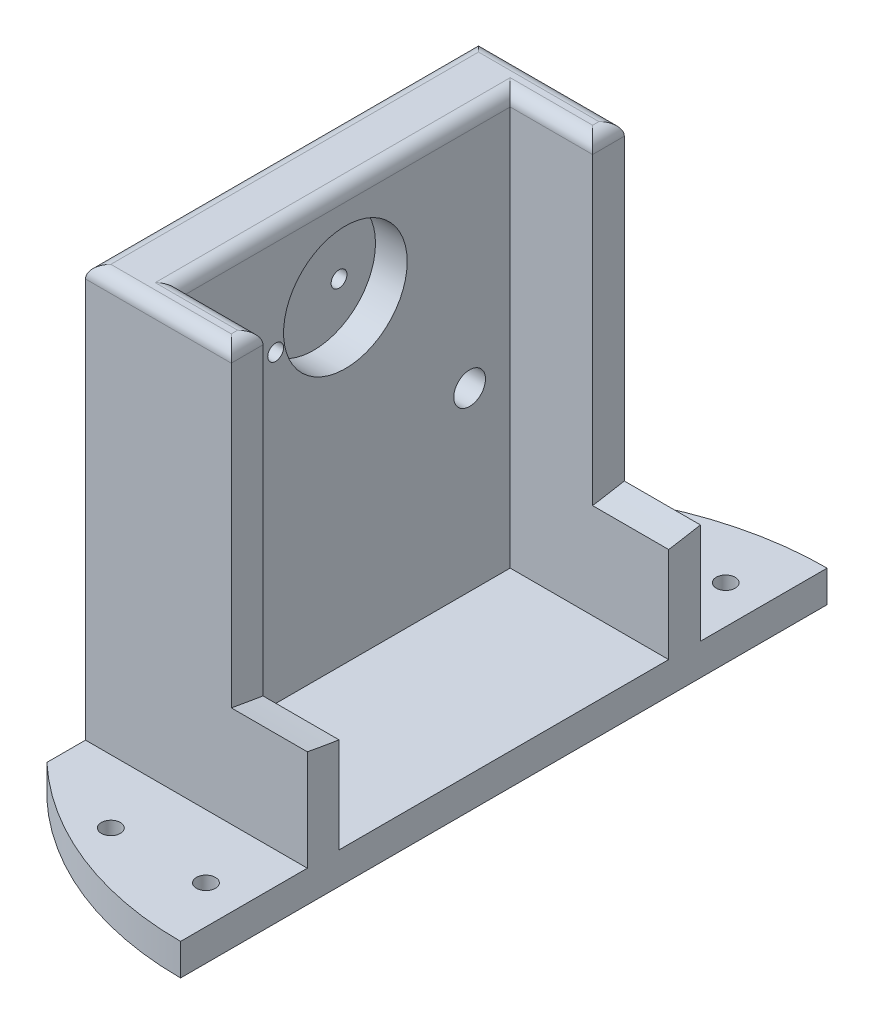
SolidWorks part; units mm, degrees
ref_plane "Plan de face" through (0, 0, 0) normal (0, 0, 1) x (1, 0, 0)
ref_plane "Plan de dessus" through (0, 0, 0) normal (0, 1, 0) x (1, 0, 0)
ref_plane "Plan de droite" through (0, 0, 0) normal (1, 0, 0) x (0, 0, -1)
sketch "Esquisse1" plane through (0, 0, 0) normal (0, 1, 0) x (1, 0, 0)
  line L0 (-50.0182, 0) -> (81.7007, 0) construction
  line L1 (0, 51) -> (0, 46)
  line L2 (-35, -31) -> (0, -31)
  line L3 (-25, -26) -> (0, -26)
  line L4 (0, 46) -> (0, -46)
  line L5 (0, 68.3448) -> (0, -68.3448) construction
  line L6 (-35, 31) -> (0, 31)
  line L7 (-25, 26) -> (0, 26)
  line L10 (0, -46) -> (0, -51)
  line L11 (25, -22.1) -> (25, -17.1)
  line L15 (25, 22.1) -> (25, 17.1)
  line L19 (-25, 26) -> (-25, -26)
  line L20 (-35, 31) -> (-35, -31)
  line L21 (-25, 17.1) -> (25, 17.1)
  line L22 (-25, 22.1) -> (25, 22.1)
  line L23 (-25, -17.1) -> (25, -17.1)
  line L24 (-25, -22.1) -> (25, -22.1)
  point P14 (-50, 0)
  point P21 (-18.8011, 42.3964)
  point P24 (-18.8306, -47.3963)
  point P33 (25, 19.6)
  point P34 (25, -19.6)
  dimension "D6" = 5
  dimension "D2" = 10
  dimension "D3" = 35
  dimension "D4" = 5
  dimension "D5" = 52
  dimension "D12" = 39.2
  dimension "D13" = 25
extrude "Boss.-Extru.7" add sketch "Esquisse1" along normal mid plane 70 contours L19 L1 L10 region at (-34.288, 0, 0)
sketch "Esquisse2" plane through (0, -35, 0) normal (0, -1, 0) x (1, 0, 0)
  line L0 (-40.1305, 0) -> (15.1892, 0) construction
  line L1 (-35, 37.0945) -> (-35, -37.0945)
  line L2 (-35, -31) -> (-35, 31) construction
  line L3 (0, 51) -> (0, -51)
  line L5 (0, 26) -> (0, 31) construction
  arc A0 (0, 51) -> (-35, 37.0945) centre (0, 0) ccw
  arc A2 (0, -51) -> (-35, -37.0945) centre (0, 0) cw
  point P9 (-35, 0)
  dimension "D1" = 51
  dimension "D2" = 51
extrude "Boss.-Extru.8" add sketch "Esquisse2" against normal blind 5
sketch "Esquisse3" plane through (-25, 0, 0) normal (1, 0, 0) x (0, 0, -1)
  line L0 (0, -101.3226) -> (0, -124.5511) construction
  line L1 (85.2632, 80.6789) -> (145.3026, 42.7808)
  line L2 (0, 28.9582) -> (0, -41.9019) construction
  line L3 (-145.3026, 42.7808) -> (-85.2632, 80.6789)
  line L4 (85.2632, 80.6789) -> (145.3026, 42.7808) construction
  line L6 (26, -30) -> (-26, -30) construction
  circle A0 centre (-19.6, -2.21) radius 2.5
  circle A1 centre (19.6, -2.21) radius 2.5
  circle A2 centre (0, 146.504) radius 150
  arc A3 (-85.2632, 80.6789) -> (85.2632, 80.6789) centre (0, 125.0981) ccw
  arc A4 (-145.3026, 42.7808) -> (145.3026, 42.7808) centre (0, 125.0981) ccw
  arc A5 (-73.5134, 63.1412) -> (43.9419, 39.5879) centre (0, 125.0981) ccw
  point P6 (0, -3.496)
  point P7 (0, 28.9582)
  dimension "D1" = 300
  dimension "D3" = 5
  dimension "D4" = 167
  dimension "D2" = 39.2
  dimension "D5" = 11.7498
  dimension "D6" = 27.79
extrude "Enlèv. mat.-Extru.1" cut sketch "Esquisse3" against normal blind 5 contours A0 | A1
sketch "Esquisse5" plane through (0, 0, 0) normal (1, 0, 0) x (0, 0, -1)
  line L0 (40.6745, 51.0324) -> (98.0512, 14.8151)
  line L1 (0, 43) -> (0, -17) construction
  line L2 (-98.0512, 14.8151) -> (-40.6745, 51.0324)
  line L3 (40.6745, 51.0324) -> (98.0512, 14.8151) construction
  line L4 (51, -35) -> (-51, -35) construction
  arc A0 (-40.6745, 51.0324) -> (40.6745, 51.0324) centre (0, 150) ccw
  arc A1 (-98.0512, 14.8151) -> (98.0512, 14.8151) centre (0, 150) ccw
  arc A3 (-28.9247, 46.9837) -> (27.706, 46.6493) centre (0, 150) ccw
  point P0 (0, 43)
  dimension "D2" = 115.478
  dimension "D3" = 60
  dimension "D7" = 167
  dimension "D4" = 18
  dimension "D10" = 11.7498
extrude "Enlèv. mat.-Extru.2" cut sketch "Esquisse5" against normal blind 12 contours L2 A1 L0 A0 | A1 | A1 region at (0, 15.8861, 0)
sketch "Esquisse6" plane through (-25, 0, 0) normal (1, 0, 0) x (0, 0, -1)
  line L1 (-26, -30) -> (26, -30) construction
  circle A0 centre (0, 20) radius 9.75
  dimension "D1" = 50
  dimension "D2" = 19.5
extrude "Enlèv. mat.-Extru.3" cut sketch "Esquisse6" against normal blind 5
fillet "Congé1" radius 2 8 edges at (-23.5, 35, -31) (-35, 35, 0) (-23.5, 35, 31) (-12, 35, -28.5) (-18.5, 35, -26) (-25, 35, 0) (-18.5, 35, 26) (-12, 35, 28.5)
sketch "Esquisse7" plane through (-35, 0, 0) normal (-1, 0, 0) x (0, 0, 1)
  line L0 (31, 33) -> (31, -30) construction
  line L1 (-29, 35) -> (29, 35) construction
  circle A0 centre (11, 18) radius 1.5
  circle A1 centre (26, 18) radius 1.5
  circle A2 centre (-4, 18) radius 1.5
  dimension "D1" = 3
  dimension "D2" = 15
  dimension "D3" = 15
  dimension "D4" = 5
  dimension "D5" = 17
sketch "Esquisse8" plane through (0, -30, 0) normal (0, 1, 0) x (1, 0, 0)
  line L0 (0, 41) -> (-29.4942, 41) construction
  line L2 (0, 51) -> (0, 31) construction
  line L3 (0, 0) -> (-35, 0) construction
  line L4 (-35, -31) -> (-35, 31) construction
  line L5 (0, -41) -> (-29.4942, -41) construction
  circle A1 centre (-21, 41) radius 1.5
  circle A2 centre (-6, 41) radius 1.5
  circle A3 centre (-6, -41) radius 1.5
  circle A4 centre (-21, -41) radius 1.5
  dimension "D1" = 3
  dimension "D2" = 15
  dimension "D3" = 6
  dimension "D4" = 10
extrude "Enlèv. mat.-Extru.5" cut sketch "Esquisse8" against normal through all
hole_wizard "Trou taraudé M31" positions "Esquisse3D1" profile "Esquisse9" tap size "M3" standard "Iso"
sketch3d "Esquisse3D1"
  point P0 (-35, 18, -4)
  point P3 (-35, 18, 11)
  point P6 (-35, 18, 26)
sketch "Esquisse9" plane through (-35, 18, -4) normal (0, 1, 0) x (0, 0, 1)
  line L0 (0, 0) -> (0, 13.2511)
  line L1 (0, 13.2511) -> (1.25, 12.5)
  line L2 (1.25, 12.5) -> (1.25, 0)
  line L5 (1.25, 0) -> (0, 0)
  line L10 (0, 13.2511) -> (-1.25, 12.5) construction
  line L11 (0, -6.35) -> (0, 107.95) construction
  dimension "Diamètre du trou pour taraudage" = 2.5
  dimension "Profondeur du trou pour taraudage" = 12.5
  dimension "Angle de pointe" = 118
cosmetic thread "Filetage de perçage1" parameters "D1"=12, "D2"=3
cosmetic thread "Filetage de perçage2" parameters "D1"=10, "D2"=3
cosmetic thread "Filetage de perçage3" parameters "D1"=5, "D2"=3
